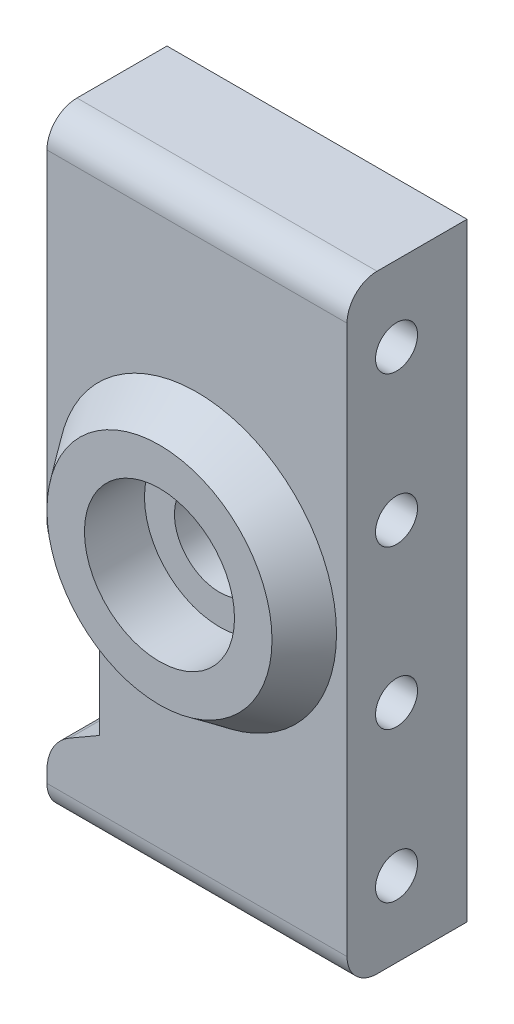
SolidWorks part; units mm, degrees
material "PLA_Holder_Ruleman"
ref_plane "Front Plane" through (0, 0, 0) normal (0, 0, 1) x (1, 0, 0)
ref_plane "Top Plane" through (0, 0, 0) normal (0, 1, 0) x (1, 0, 0)
ref_plane "Right Plane" through (0, 0, 0) normal (1, 0, 0) x (0, 0, -1)
sketch "Sketch1" plane through (0, 0, 0) normal (0, 0, 1) x (1, 0, 0)
  line L0 (-10, 20.2804) -> (-10, -20.2804)
  line L1 (-10, -20.2804) -> (10, -20.2804)
  line L2 (10, -20.2804) -> (10, 20.2804)
  line L3 (10, 20.2804) -> (-10, 20.2804)
  line L4 (-10, 20.2804) -> (10, -20.2804) construction
  line L11 (-10, -20.2804) -> (10, 20.2804) construction
  point P9 (0, 0)
  dimension "D1" = 20
  dimension "D2" = 40.5608
extrude "Boss-Extrude1" add sketch "Sketch1" against normal blind 8
sketch "Sketch6" plane through (10, 0, 0) normal (1, 0, 0) x (0, 0, -1)
  line L0 (0, -20.2804) -> (0, 20.2804) construction
  line L1 (3.3, -5.2652) -> (3.3, -15.2652) construction
  line L2 (3.3, 4.95) -> (3.3, 15.6283) construction
  line L3 (0, 0) -> (8, 0) construction
  line L4 (8, -20.2804) -> (8, 20.2804) construction
  line L5 (23.2424, -10.2652) -> (-16.6424, -10.2652) construction
  line L6 (8, -20.2804) -> (0, -20.2804) construction
  line L7 (23.2424, -0.25) -> (-16.6424, -0.25) construction
  circle A0 centre (3.3, -15.2652) radius 1.4
  circle A1 centre (3.3, -5.2652) radius 1.4
  circle A2 centre (3.3, 15.2652) radius 1.4
  circle A3 centre (3.3, 5.2652) radius 1.4
  point P15 (3.3, -10.2652)
  dimension "D1" = 2.8
  dimension "D2" = 4.7
  dimension "D3" = 10.0152
  dimension "D4" = 10
  dimension "D5" = 10.0152
extrude "Cut-Extrude1" cut sketch "Sketch6" against normal blind 10
sketch "Sketch8" plane through (0, 0, 0) normal (0, 0, 1) x (1, 0, 0)
  line L0 (-10, 20.2804) -> (10, -20.2804) construction
  circle A0 centre (0, 0) radius 7.5
  dimension "D1" = 15
extrude "Boss-Extrude2" add sketch "Sketch8" along normal blind 2.5
sketch "Sketch9" plane through (0, 0, 2.5) normal (0, 0, 1) x (1, 0, 0)
  circle A0 centre (0, 0) radius 5
  dimension "D1" = 10
extrude "Cut-Extrude3" cut sketch "Sketch9" against normal blind 4
sketch "Sketch10" plane through (0, 0, -1.5) normal (0, 0, 1) x (1, 0, 0)
  circle A0 centre (0, 0) radius 3
  dimension "D1" = 6
extrude "Cut-Extrude4" cut sketch "Sketch10" against normal up to surface (6.5 mm away) up to face at (0, 0, -8)
fillet "Fillet1" radius 2 2 edges at (0, -20.2804, 0) (0, 20.2804, 0) tangent propagation no
chamfer "Chamfer1" distance 1.8 distance2 2.5 1 edges at (7.5, 0, 0) first distance on face at (7.5, 0, 0)
sketch "Sketch11" plane through (-10, 0, 0) normal (-1, 0, 0) x (0, 0, 1)
  line L0 (-8, -10.2652) -> (0, -10.2652) construction
  line L1 (-8, 20.2804) -> (-8, -20.2804) construction
  line L2 (0, 18.2804) -> (0, -18.2804) construction
  line L3 (-8, -20.2804) -> (-2, -20.2804) construction
  line L4 (-8, -13.7652) -> (0, -13.7652)
  line L5 (-8, -6.7652) -> (0, -6.7652)
  line L6 (0, -6.7652) -> (0, -13.7652)
  line L7 (-8, -13.7652) -> (-8, -6.7652)
  dimension "D1" = 10.0152
  dimension "D2" = 3.5
  dimension "D3" = 3.5
extrude "Cut-Extrude5" cut sketch "Sketch11" against normal blind 3.5
chamfer "Chamfer2" distance 3.5 angle 30 2 edges at (-10, -13.7652, -4) (-10, -6.7652, -4) first distance on face at (-8.25, -13.7652, -4) first distance on face at (-8.25, -6.7652, -4)
fillet "Fillet2" radius 3 2 edges at (-10, -15.7859, -4) (-10, -4.7444, -4)
